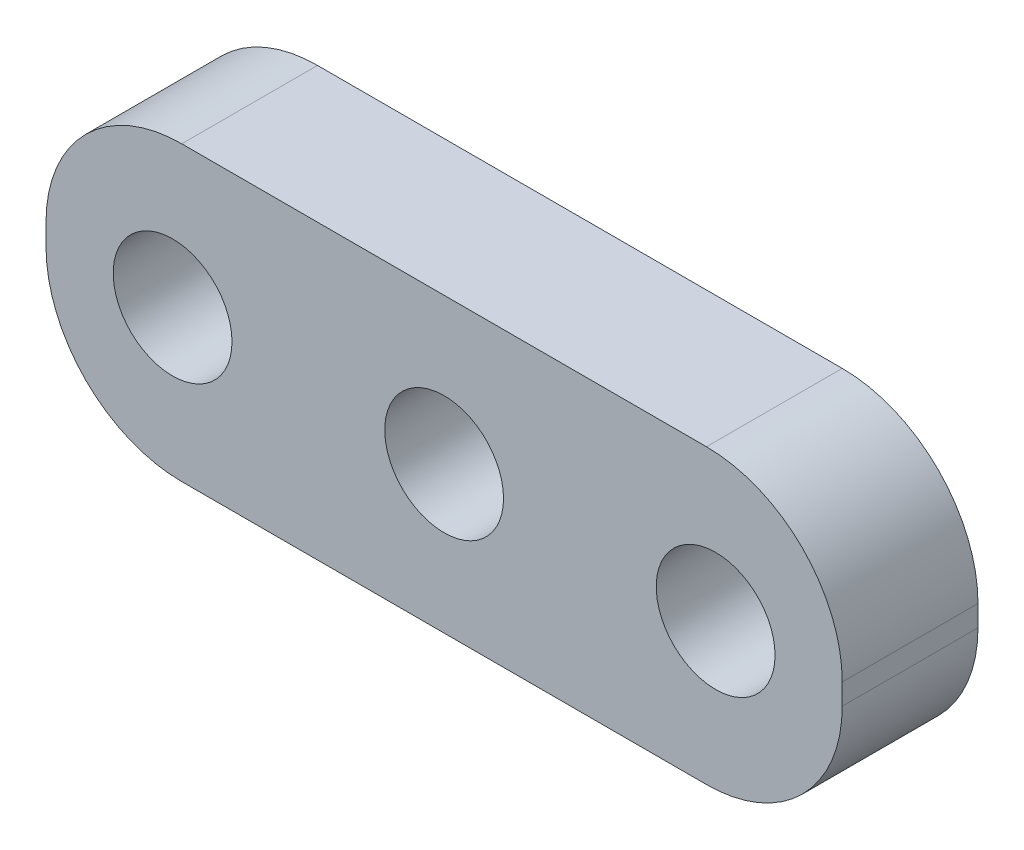
SolidWorks part; units mm, degrees
ref_plane "Front Plane" through (0, 0, 0) normal (0, 0, 1) x (1, 0, 0)
ref_plane "Top Plane" through (0, 0, 0) normal (0, 1, 0) x (1, 0, 0)
ref_plane "Right Plane" through (0, 0, 0) normal (1, 0, 0) x (0, 0, -1)
sketch "Sketch1" plane through (0, 0, 0) normal (0, 0, 1) x (1, 0, 0)
  line L0 (12.738, 0) -> (-12.738, 0) construction
  line L1 (11.73, -4.31) -> (-11.73, -4.31)
  line L2 (11.73, -4.31) -> (11.73, 4.31)
  line L3 (11.73, 4.31) -> (-11.73, 4.31)
  line L4 (-11.73, -4.31) -> (-11.73, 4.31)
  circle A0 centre (-8, 0) radius 1.75
  circle A1 centre (8, 0) radius 1.75
  circle A2 centre (0, 0) radius 1.75
  point P4 (11.73, 0)
  point P6 (0, 4.31)
  dimension "D1" = 3.73
  dimension "D3" = 16
  dimension "D2" = 3.73
extrude "Boss-Extrude1" add sketch "Sketch1" along normal blind 4
fillet "Fillet1" radius 4 4 edges at (11.73, -4.31, 2) (11.73, 4.31, 2) (-11.73, 4.31, 2) (-11.73, -4.31, 2)
